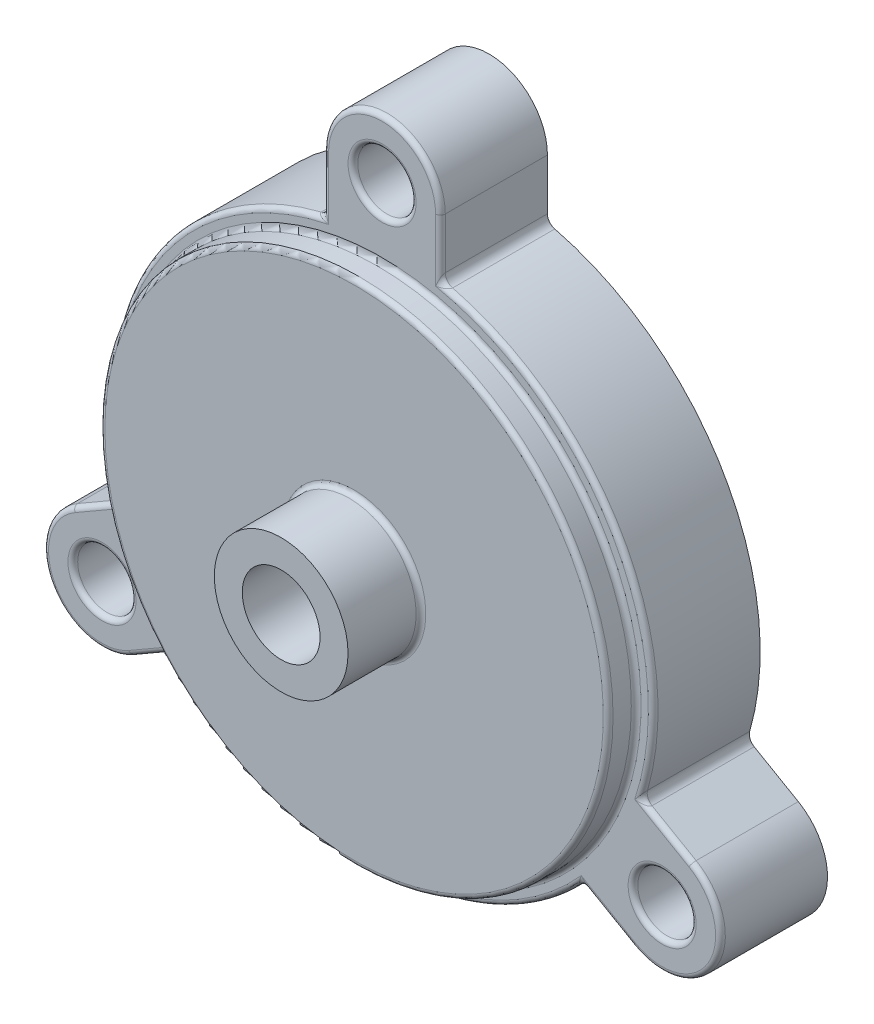
SolidWorks part; units mm, degrees
material "PE Low/Medium Density"
ref_plane "Front Plane" through (0, 0, 0) normal (0, 0, 1) x (1, 0, 0)
ref_plane "Top Plane" through (0, 0, 0) normal (0, 1, 0) x (1, 0, 0)
ref_plane "Right Plane" through (0, 0, 0) normal (1, 0, 0) x (0, 0, -1)
sketch "Sketch1" plane through (0, 0, 0) normal (1, 0, 0) x (0, 0, -1)
  line L0 (1.4605, 14.1605) -> (1.4605, 13.2715)
  line L1 (0, 0) -> (7.62, 0) construction
  line L2 (0, 12.2555) -> (0, 13.2715)
  line L3 (1.4605, 14.1605) -> (7.0485, 14.1605)
  line L4 (7.62, 12.2555) -> (7.62, 12.9159)
  line L5 (1.4605, 13.2715) -> (0, 13.2715)
  line L6 (7.0485, 14.1605) -> (7.0485, 12.9159)
  line L7 (7.0485, 12.9159) -> (7.62, 12.9159)
  line L8 (0, 12.2555) -> (0, 0)
  line L9 (0, 0) -> (1.4605, 0)
  line L10 (7.62, 12.2555) -> (1.4605, 12.2555)
  line L11 (1.4605, 12.2555) -> (1.4605, 0)
  dimension "D1" = 5.588
  dimension "D2" = 7.62
  dimension "D3" = 0.5715
  dimension "D4" = 14.1605
  dimension "D5" = 1.016
  dimension "D6" = 1.905
  dimension "D7" = 0.6604
revolve "Base revolve" add sketch "Sketch1" angle 360 about L1
sketch "Sketch3" plane through (0, 0, -7.0485) normal (0, 0, -1) x (-1, 0, 0)
  line L0 (-3.048, 16.891) -> (-3.048, 13.8286)
  line L1 (3.048, 16.891) -> (3.048, 13.8286)
  line L2 (0, 0) -> (0, 22.6145) construction
  arc A0 (3.048, 16.891) -> (-3.048, 16.891) centre (0, 16.891) ccw
  circle A1 centre (0, 0) radius 14.1605 construction
  circle A2 centre (0, 16.891) radius 1.524
  arc A3 (-3.048, 13.8286) -> (3.048, 13.8286) centre (0, 0) cw
  point P12 (0, 19.939)
  dimension "D1" = 3.048
  dimension "D2" = 3.048
  dimension "D3" = 16.891
extrude "Flange" add sketch "Sketch3" against normal up to surface (5.588 mm away) up to face at (13.2715, 0, -1.4605)
pattern_circular "Circular pattern for flanges" count 3 over 360 about axis through (0, 0, 0) along (0, 0, 1) of "Flange"
sketch "Sketch4" plane through (0, 0, -7.62) normal (0, 0, -1) x (-1, 0, 0)
  line L0 (-1.524, 14.2514) -> (-1.524, 12.1604)
  line L1 (1.524, 14.2514) -> (1.524, 12.1604)
  line L2 (-1.524, 16.891) -> (-1.524, 14.2514) construction
  line L3 (1.524, 16.891) -> (1.524, 14.2514) construction
  arc A0 (-1.524, 14.2514) -> (1.524, 14.2514) centre (0, 16.891) ccw
  circle A1 centre (0, 16.891) radius 1.524 construction
  circle A2 centre (0, 0) radius 12.2555 construction
  circle A3 centre (0, 0) radius 12.2555 construction
  arc A4 (-1.524, 12.1604) -> (1.524, 12.1604) centre (0, 0) cw
extrude "Flange cut" cut sketch "Sketch4" against normal blind 5.842
pattern_circular "Circular pattern for flange cut" count 3 over 360 about axis through (0, 0, 0) along (0, 0, 1) of "Flange cut"
sketch "Sketch5" plane through (0, 0, 0) normal (0, 0, 1) x (1, 0, 0)
  circle A0 centre (0, 0) radius 3.4925
  dimension "D1" = 6.985
extrude "Hub" add sketch "Sketch5" along normal blind 3.81 and the other way blind 2.921
sketch "Sketch6" plane through (0, 0, 3.81) normal (0, 0, 1) x (1, 0, 0)
  circle A0 centre (0, 0) radius 2.032
  dimension "D1" = 4.064
extrude "Bore" cut sketch "Sketch6" against normal through all
fillet "Touch-up fillets" radius 0.254 18 edges at (13.2715, 0, 0) (-3.4925, 0, 0) (13.104, -8.4455, -1.4605) (-16.152, -8.4455, -1.4605) (-1.524, 16.891, -1.4605) (-3.048, 15.3598, -1.4605) (0, 19.939, -1.4605) (3.048, 15.3598, -1.4605) (12.2634, 7.0803, -1.4605) (14.826, -5.0402, -1.4605) (17.2677, -9.9695, -1.4605) (11.778, -10.3195, -1.4605) (0, -14.1605, -1.4605) (-11.778, -10.3195, -1.4605) (-17.2677, -9.9695, -1.4605) (-14.826, -5.0402, -1.4605) (-12.2634, 7.0802, -1.4605) (13.2715, 0, -1.4605)
fillet "Flange fillet" radius 0.508 12 edges at (-3.0105, 13.7984, -1.5817) (-13.455, -4.292, -1.5817) (-10.4445, -9.5064, -1.5817) (10.4445, -9.5064, -1.5817) (13.455, -4.292, -1.5817) (3.0105, 13.7984, -1.5817) (-3.048, 13.8286, -4.3815) (-13.4999, -4.2746, -4.3815) (-10.4519, -9.5539, -4.3815) (10.4519, -9.5539, -4.3815) (13.4999, -4.2746, -4.3815) (3.048, 13.8286, -4.3815)
